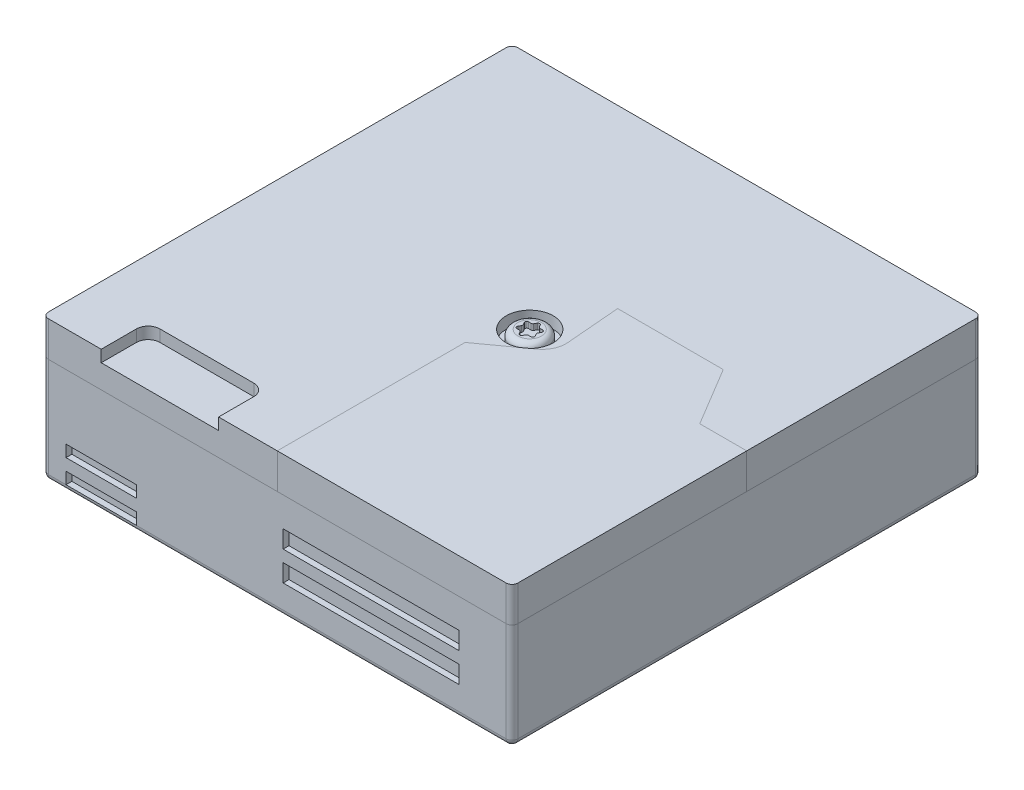
SolidWorks part; units mm, degrees
ref_plane "Front Plane" through (0, 0, 0) normal (0, 0, 1) x (1, 0, 0)
ref_plane "Top Plane" through (0, 0, 0) normal (0, 1, 0) x (1, 0, 0)
ref_plane "Right Plane" through (0, 0, 0) normal (1, 0, 0) x (0, 0, -1)
sketch "Sketch1" plane through (0, 0, 0) normal (0, 1, 0) x (1, 0, 0)
  line L1 (0, 0) -> (40, 0)
  line L2 (0, 0) -> (0, 40)
  line L3 (0, 40) -> (40, 40)
  line L4 (40, 0) -> (40, 40)
  dimension "D1" = 40
  dimension "D2" = 40
extrude "Boss-Extrude1" add sketch "Sketch1" against normal blind 9
extrude "Boss-Extrude2" add sketch "Sketch1<2>" along normal blind 3 separate body
sketch "Sketch1<2>" plane through (0, 0, 0) normal (0, 1, 0) x (1, 0, 0) same geometry as "Sketch1"
sketch "Sketch2" plane through (0, 0, -40) normal (0, 0, -1) x (-1, 0, 0)
  line L0 (0, -9) -> (-40, -9) construction
  line L1 (-38, -6) -> (-28, -6)
  line L2 (-38, -6) -> (-38, -2)
  line L3 (-38, -2) -> (-28, -2)
  line L4 (-28, -6) -> (-28, -2)
  line L5 (-40, -9) -> (-40, 0) construction
  dimension "D1" = 10
  dimension "D2" = 4
  dimension "D3" = 3
  dimension "D4" = 2
extrude "Cut-Extrude1" cut sketch "Sketch2" against normal blind 4
sketch "Sketch3" plane through (0, 3, 0) normal (0, 1, 0) x (1, 0, 0)
  line L0 (20, 0) -> (40, 0)
  line L1 (0, 0) -> (40, 0) construction
  line L2 (40, 0) -> (40, 20)
  line L3 (40, 0) -> (40, 40) construction
  line L4 (40, 20) -> (36, 20)
  line L5 (36, 20) -> (33, 25)
  line L6 (33, 25) -> (24, 25)
  line L7 (24, 25) -> (24.3884, 20.3695)
  line L8 (23.5679, 18.5822) -> (20, 16)
  line L9 (20, 16) -> (20, 0)
  arc A0 (24.3884, 20.3695) -> (23.5679, 18.5822) centre (22.3954, 20.2024) cw
  point P16 (30, 0)
  dimension "D6" = 2
  dimension "D1" = 25
  dimension "D2" = 9
  dimension "D3" = 7
  dimension "D4" = 4
  dimension "D5" = 16
extrude "Cut-Extrude3" cut sketch "Sketch3" against normal blind 3
extrude "Boss-Extrude4" add sketch "Sketch3<3>" against normal blind 3 separate body
sketch "Sketch3<3>" plane through (0, 3, 0) normal (0, 1, 0) x (1, 0, 0) same geometry as "Sketch3"
sketch "Sketch4" plane through (0, 3, 0) normal (0, 1, 0) x (1, 0, 0)
  line L0 (0, 0) -> (20, 0) construction
  line L1 (5, 0) -> (15, 0)
  line L2 (5, 0) -> (5, 3)
  line L3 (6, 4) -> (14, 4)
  line L4 (15, 0) -> (15, 3)
  line L5 (0, 40) -> (0, 0) construction
  circle A0 centre (21.7852, 19.7264) radius 2
  arc A1 (14, 4) -> (15, 3) centre (14, 3) cw
  arc A2 (5, 3) -> (6, 4) centre (6, 3) cw
  point P11 (15, 4)
  point P14 (5, 4)
  dimension "D3" = 1
  dimension "D5" = 4
  dimension "D1" = 10
  dimension "D2" = 4
  dimension "D4" = 5
extrude "Cut-Extrude4" cut sketch "Sketch4" against normal blind 1
sketch "Sketch5" plane through (0, 2, 0) normal (0, 1, 0) x (1, 0, 0)
  line L0 (21.4099, 20.2264) -> (21.179, 20.2264)
  line L1 (22.5213, 19.4514) -> (22.4059, 19.6514)
  line L2 (21.6553, 20.5014) -> (21.5398, 20.3014)
  line L3 (21.179, 19.2264) -> (21.4099, 19.2264)
  line L4 (21.9151, 18.9514) -> (22.0306, 19.1514)
  line L5 (22.3914, 20.2264) -> (22.1605, 20.2264)
  line L6 (21.0491, 20.0014) -> (21.1646, 19.8014)
  line L7 (22.0306, 20.3014) -> (21.9151, 20.5014)
  line L8 (21.1646, 19.6514) -> (21.0491, 19.4514)
  line L9 (21.5398, 19.1514) -> (21.6553, 18.9514)
  line L11 (22.1605, 19.2264) -> (22.3914, 19.2264)
  line L12 (22.4059, 19.8014) -> (22.5213, 20.0014)
  circle A0 centre (21.7852, 19.7264) radius 1.5
  circle A1 centre (21.7852, 19.7264) radius 0.5 construction
  circle A2 centre (21.7852, 19.7264) radius 0.5 construction
  arc A3 (22.1605, 20.2264) -> (22.0306, 20.3014) centre (22.1605, 20.3764) cw
  arc A4 (22.5213, 20.0014) -> (22.3914, 20.2264) centre (22.3914, 20.0764) ccw
  arc A5 (22.4059, 19.8014) -> (22.4059, 19.6514) centre (22.5358, 19.7264) ccw
  arc A6 (22.5213, 19.4514) -> (22.3914, 19.2264) centre (22.3914, 19.3764) cw
  arc A7 (22.1605, 19.2264) -> (22.0306, 19.1514) centre (22.1605, 19.0764) ccw
  arc A8 (21.9151, 18.9514) -> (21.6553, 18.9514) centre (21.7852, 19.0264) cw
  arc A9 (21.5398, 19.1514) -> (21.4099, 19.2264) centre (21.4099, 19.0764) ccw
  arc A10 (21.0491, 19.4514) -> (21.179, 19.2264) centre (21.179, 19.3764) ccw
  arc A11 (21.1646, 19.6514) -> (21.1646, 19.8014) centre (21.0347, 19.7264) ccw
  arc A12 (21.179, 20.2264) -> (21.0491, 20.0014) centre (21.179, 20.0764) ccw
  arc A13 (21.4099, 20.2264) -> (21.5398, 20.3014) centre (21.4099, 20.3764) ccw
  arc A14 (21.9151, 20.5014) -> (21.6553, 20.5014) centre (21.7852, 20.4264) ccw
  point P16 (22.0739, 20.2264)
  dimension "D1" = 0.15
  dimension "D2" = 3
  dimension "D3" = 1
extrude "Boss-Extrude6" add sketch "Sketch5" along normal blind 1 separate body
extrude "Boss-Extrude7" add sketch "Sketch5<2>" along normal blind 0.5 separate body contours L7 A14 L2 A13 L0 A12 L6 A11 L8 A10 L3 A9 L9 A8 L4 A7 L11 A6 L1 A5 L12 A4 L5 A3 region at (21.7852, 2, -19.7264)
sketch "Sketch5<2>" plane through (0, 2, 0) normal (0, 1, 0) x (1, 0, 0) same geometry as "Sketch5"
fillet "Fillet1" radius 0.5 1 edges at (21.7852, 3, -18.2264)
fillet "Fillet2" radius 0.5 3 edges at (0, 1.5, 0) (40, 1.5, -40) (0, 1.5, -40)
fillet "Fillet3" radius 0.5 8 edges at (20, -9, 0) (40, -9, -20) (20, -9, -40) (0, -9, -20) (40, -4.5, -40) (40, -4.5, 0) (0, -4.5, 0) (0, -4.5, -40)
fillet "Fillet4" radius 0.5 1 edges at (40, 1.5, 0)
sketch "Sketch6" plane through (0, 0, 0) normal (0, 0, 1) x (1, 0, 0)
  line L0 (0.5, -8.5) -> (39.5, -8.5) construction
  line L1 (2, -8.5) -> (8, -8.5)
  line L2 (2, -8.5) -> (2, -7.5)
  line L3 (2, -7.5) -> (8, -7.5)
  line L4 (8, -8.5) -> (8, -7.5)
  line L5 (0, -8.5) -> (0, 0) construction
  line L6 (2, -6.5) -> (8, -6.5)
  line L7 (2, -6.5) -> (2, -5.5)
  line L8 (2, -5.5) -> (8, -5.5)
  line L9 (8, -6.5) -> (8, -5.5)
  line L10 (20.5, -2.5) -> (35.5, -2.5)
  line L11 (20.5, -2.5) -> (20.5, -4)
  line L12 (20.5, -4) -> (35.5, -4)
  line L13 (35.5, -2.5) -> (35.5, -4)
  line L14 (20.5, -5) -> (35.5, -5)
  line L15 (20.5, -5) -> (20.5, -6.5)
  line L16 (20.5, -6.5) -> (35.5, -6.5)
  line L17 (35.5, -5) -> (35.5, -6.5)
  line L18 (39.5, -8.5) -> (39.5, 0) construction
  line L19 (39.5, -9) -> (0.5, -9) construction
  point P22 (35.5, -5.75)
  dimension "D1" = 6
  dimension "D2" = 1
  dimension "D3" = 2
  dimension "D4" = 1
  dimension "D5" = 15
  dimension "D6" = 1.5
  dimension "D7" = 4
  dimension "D8" = 1
  dimension "D9" = 2.5
extrude "Cut-Extrude5" cut sketch "Sketch6" against normal blind 0.5
